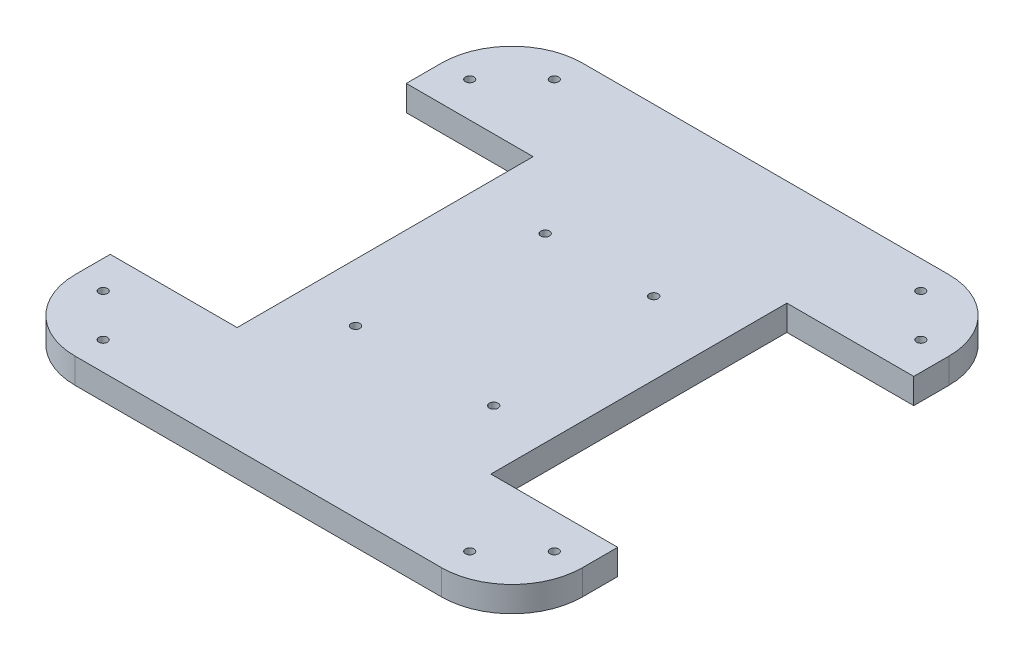
SolidWorks part; units mm, degrees
ref_plane "Front Plane" through (0, 0, 0) normal (0, 0, 1) x (1, 0, 0)
ref_plane "Top Plane" through (0, 0, 0) normal (0, 1, 0) x (1, 0, 0)
ref_plane "Right Plane" through (0, 0, 0) normal (1, 0, 0) x (0, 0, -1)
sketch "Sketch1" plane through (0, 0, 0) normal (0, 1, 0) x (1, 0, 0)
  line L1 (-65, -90) -> (65, -90)
  line L2 (-90, -65) -> (-90, 65)
  line L3 (-65, 90) -> (65, 90)
  line L4 (90, -65) -> (90, 65)
  arc A0 (-90, 65) -> (-65, 90) centre (-65, 65) cw
  arc A1 (65, 90) -> (90, 65) centre (65, 65) cw
  arc A2 (90, -65) -> (65, -90) centre (65, -65) cw
  arc A3 (-65, -90) -> (-90, -65) centre (-65, -65) cw
  point P4 (-90, 0)
  point P6 (0, 90)
  dimension "D3" = 25
  dimension "D1" = 180
  dimension "D2" = 180
extrude "Plate" add sketch "Sketch1" along normal blind 9
sketch "Sketch3" plane through (0, 9, 0) normal (0, 1, 0) x (1, 0, 0)
  line L0 (-65, 90) -> (-65, -90) construction
  line L1 (65, 90) -> (65, -90) construction
  line L2 (-90, 65) -> (90, 65) construction
  line L3 (-90, -65) -> (90, -65) construction
  circle A0 centre (-65, 80) radius 1.525
  circle A1 centre (-80, 65) radius 1.525
  circle A2 centre (80, 65) radius 1.525
  circle A3 centre (80, -65) radius 1.525
  circle A4 centre (65, 80) radius 1.525
  circle A5 centre (65, -80) radius 1.525
  circle A6 centre (-65, -80) radius 1.525
  circle A7 centre (-80, -65) radius 1.525
  dimension "D1" = 3.05
  dimension "D2" = 15
  dimension "D3" = 15
  dimension "D4" = 15
  dimension "D5" = 15
  dimension "D6" = 15
  dimension "D7" = 15
  dimension "D8" = 15
  dimension "D9" = 15
extrude "Hex Holes" cut sketch "Sketch3" against normal through all
sketch "Sketch4" plane through (0, 9, 0) normal (0, 1, 0) x (1, 0, 0)
  line L0 (-90, -65) -> (-90, 65) construction
  line L1 (-65, -90) -> (65, -90) construction
  circle A0 centre (-24.5, -31) radius 1.55
  circle A1 centre (24.5, -31) radius 1.55
  circle A2 centre (-19.25, 31) radius 1.55
  circle A3 centre (19.25, 31) radius 1.55
  dimension "D1" = 3.1
  dimension "D2" = 62
  dimension "D3" = 49
  dimension "D4" = 5.25
  dimension "D5" = 38.5
  dimension "D6" = 65.5
  dimension "D7" = 59
extrude "Arduino Holes" cut sketch "Sketch4" against normal through all
sketch "Sketch5" plane through (0, 9, 0) normal (0, 1, 0) x (1, 0, 0)
  line L0 (-90, 52.5) -> (-45, 52.5)
  line L1 (-90, -65) -> (-90, 65) construction
  line L2 (-45, 52.5) -> (-45, -52.5)
  line L3 (-45, -52.5) -> (-90, -52.5)
  line L4 (-90, 52.5) -> (-90, -52.5)
  line L5 (90, -65) -> (90, 65) construction
  line L6 (90, 52.5) -> (45, 52.5)
  line L7 (90, 52.5) -> (90, -52.5)
  line L8 (90, -52.5) -> (45, -52.5)
  line L9 (45, 52.5) -> (45, -52.5)
  line L10 (-90, 0) -> (90, 0) construction
  point P16 (-90, 0)
  point P17 (90, 0)
  dimension "D1" = 105
  dimension "D2" = 45
extrude "Cut-Extrude1" cut sketch "Sketch5" against normal through all
